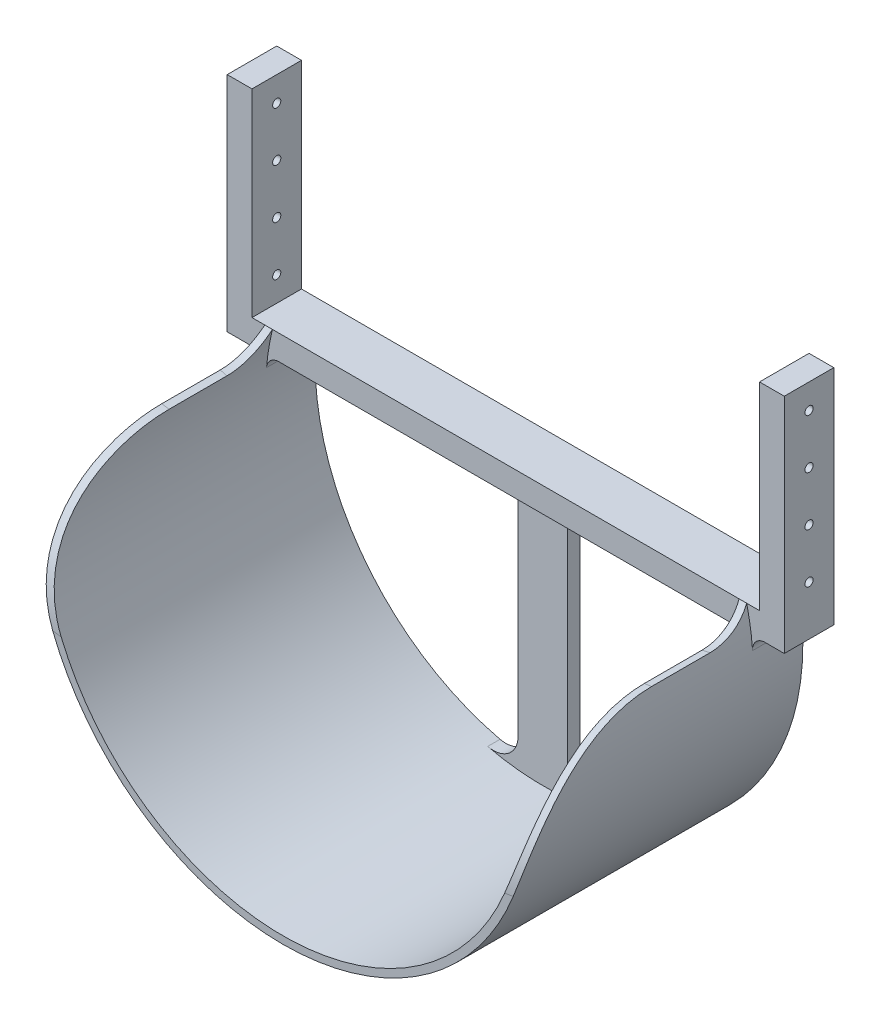
SolidWorks part; units mm, degrees
ref_plane "정면" through (0, 0, 0) normal (0, 0, 1) x (1, 0, 0)
ref_plane "윗면" through (0, 0, 0) normal (0, 1, 0) x (1, 0, 0)
ref_plane "우측면" through (0, 0, 0) normal (1, 0, 0) x (0, 0, -1)
sketch "스케치1" plane through (0, 0, 0) normal (0, 0, 1) x (1, 0, 0)
  line L0 (-112.5, 80) -> (-112.5, -10)
  line L2 (-102.5, 80) -> (-102.5, 0)
  line L3 (-102.5, 0) -> (102.5, 0)
  line L4 (102.5, 80) -> (102.5, 0)
  line L5 (-112.5, -10) -> (112.5, -10)
  line L6 (112.5, 80) -> (112.5, -10)
  line L8 (-102.5, 80) -> (-112.5, 80)
  line L9 (102.5, 80) -> (112.5, 80)
  line L10 (-112.5, 90) -> (-112.5, -10) construction
  line L11 (112.5, 90) -> (112.5, -10) construction
  line L12 (-112.5, 90) -> (112.5, 90) construction
  line L13 (-102.5, 80) -> (102.5, 80) construction
  dimension "D1" = 205
  dimension "D2" = 80
  dimension "D3" = 10
extrude "보스-돌출1" add sketch "스케치1" along normal blind 20
sketch "스케치2" plane through (0, 0, 0) normal (1, 0, 0) x (0, 0, -1)
  line L0 (0, -10) -> (0, 80) construction
  line L1 (-20, 80) -> (0, 80) construction
  circle A0 centre (-10, 70) radius 1.65
  circle A1 centre (-10, 50) radius 1.65
  circle A2 centre (-10, 30) radius 1.65
  circle A3 centre (-10, 10) radius 1.65
  circle A5 centre (-10, -10) radius 1.65 [skipped]
  dimension "D3" = 3.3
  dimension "D1" = 10
  dimension "D2" = 10
  dimension "D4" = 5
extrude "컷-돌출1" cut sketch "스케치2" against normal through all both and the other way through all
sketch "스케치5" plane through (0, 0, 0) normal (0, 0, 1) x (1, 0, 0)
  line L1 (-10, 0) -> (10, 0)
  line L2 (-10, 0) -> (-10, -120)
  line L3 (-10, -120) -> (10, -120)
  line L4 (10, 0) -> (10, -120)
  dimension "D1" = 20
  dimension "D2" = 120
extrude "보스-돌출2" add sketch "스케치5" along normal blind 5
chamfer "모따기1" distance 10 angle 45 1 edges at (0, -10, 5)
chamfer "모따기2" distance 10 angle 45 2 edges at (-10, -10, 7.5) (10, -10, 7.5)
sketch "스케치7" plane through (0, 0, 0) normal (0, 0, 1) x (1, 0, 0)
  line L0 (0, 0) -> (0, -120) construction
  line L1 (-10, -120) -> (10, -120) construction
  line L2 (-98.9175, -8.326) -> (-95.95, -8.7663)
  line L3 (95.95, -8.7663) -> (98.9175, -8.326)
  arc A0 (-95.95, -8.7663) -> (95.95, -8.7663) centre (0, -23) ccw
  arc A1 (-98.9175, -8.326) -> (98.9175, -8.326) centre (0, -23) ccw
  point P4 (0, -120)
  dimension "D2" = 100
  dimension "D1" = 3
extrude "보스-돌출3" add sketch "스케치7" along normal blind 110
fillet "필렛1" radius 10 2 edges at (-10, -119.4832, 2.5) (10, -119.4832, 2.5)
fillet "필렛2" radius 50 2 edges at (-97.4338, -8.5462, 110) (97.4338, -8.5462, 110)
fillet "필렛3" radius 20 2 edges at (97.4338, -8.5462, 20) (-97.4338, -8.5462, 20)
fillet "필렛4" radius 5 4 edges at (-96.1249, -10, 10) (96.1249, -10, 10) (99.1514, -10, 10) (-99.1514, -10, 10)
